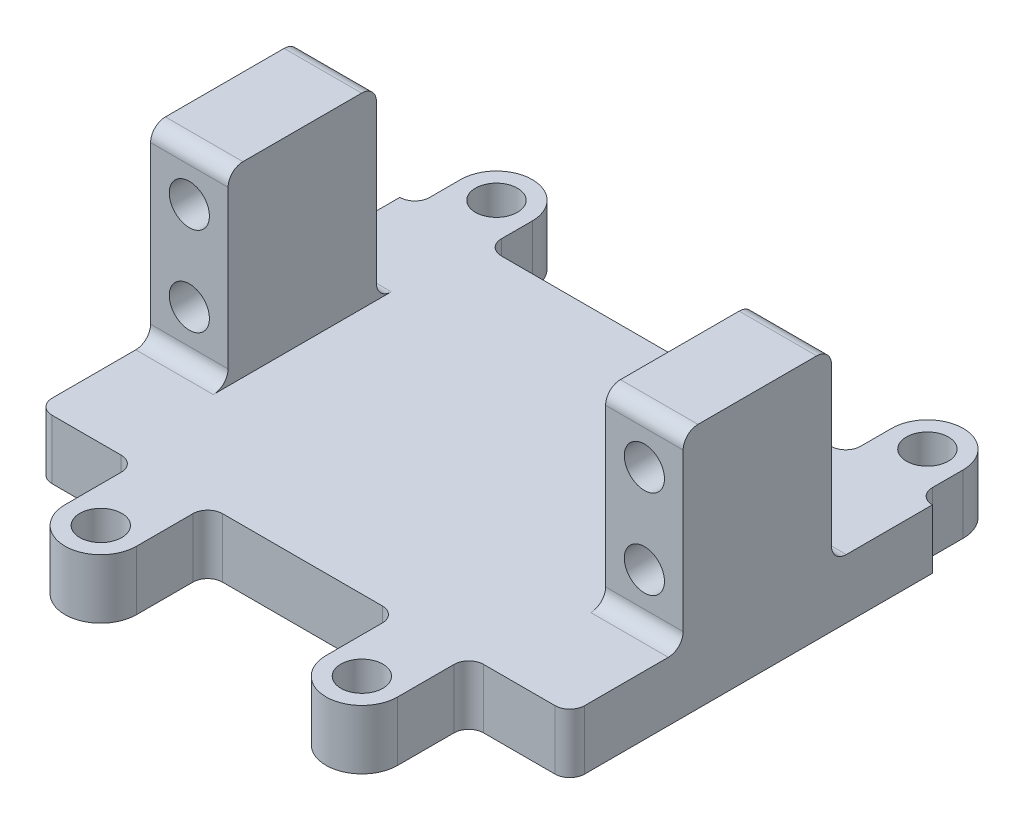
SolidWorks part; units mm, degrees
ref_plane "Front Plane" through (0, 0, 0) normal (0, 0, 1) x (1, 0, 0)
ref_plane "Top Plane" through (0, 0, 0) normal (0, 1, 0) x (1, 0, 0)
ref_plane "Right Plane" through (0, 0, 0) normal (1, 0, 0) x (0, 0, -1)
sketch "Sketch1" plane through (0, 0, 0) normal (0, 1, 0) x (1, 0, 0)
  line L1 (0, 0) -> (54.4, 0)
  line L2 (0, 0) -> (0, 38.8)
  line L3 (0, 38.8) -> (54.4, 38.8)
  line L4 (54.4, 0) -> (54.4, 38.8)
  dimension "D1" = 54.4
  dimension "D2" = 38.8
extrude "Boss-Extrude1" add sketch "Sketch1" along normal blind 3.175
sketch "Sketch2" plane through (0, 3.175, 0) normal (0, 1, 0) x (1, 0, 0)
  line L0 (0, 38.8) -> (0, 0) construction
  line L1 (0, 28) -> (7, 28)
  line L2 (0, 28) -> (0, 12.125)
  line L3 (0, 12.125) -> (7, 12.125)
  line L4 (7, 28) -> (7, 12.125)
  line L5 (54.4, 38.8) -> (0, 38.8) construction
  dimension "D1" = 15.875
  dimension "D2" = 10.8
  dimension "D3" = 7
extrude "Boss-Extrude2" add sketch "Sketch2" along normal blind 20
ref_plane "Plane1" through (27.2, 0, 0) normal (-1, 0, 0) x (0, 0, 1)
mirror "Mirror1" about plane through (27.2, 0, 0) normal (-1, 0, 0) of "Boss-Extrude2"
sketch "Sketch3" plane through (0, 3.175, 0) normal (0, 1, 0) x (1, 0, 0)
  line L0 (9.2746, -7.608) -> (9.2746, 0)
  line L1 (0, 0) -> (54.4, 0) construction
  line L2 (16.9454, -7.608) -> (16.9454, 0)
  circle A0 centre (13.11, -7.608) radius 2.2479
  circle A2 centre (13.11, -7.608) radius 3.8354
  line M12 (0, 0) -> (54.4, 0)
  dimension "D1" = 4.4958
  dimension "D4" = 1.5875
  dimension "D2" = 7.608
  dimension "D3" = 13.11
extrude "Boss-Extrude3" add sketch "Sketch3" against normal up to surface (3.175 mm away) contours A2 A0 | A2 L2 L0 M12 region at (13.11, 3.175, 2.3776) region at (13.11, 3.175, 3.8811) up to face at (27.2, 0, -19.4)
pattern_linear "LPattern1" count 2 spacing 27.94 along (1, 0, 0) of "Boss-Extrude3"
sketch "Sketch6" plane through (0, 3.175, 0) normal (0, 1, 0) x (1, 0, 0)
  line L0 (0, 38.8) -> (0, 28) construction
  line L1 (0.3048, 43.7) -> (0.3048, 38.8)
  line L2 (7.9756, 43.7) -> (7.9756, 38.8)
  line L3 (54.4, 38.8) -> (0, 38.8) construction
  circle A0 centre (4.1402, 43.7) radius 2.2479
  circle A1 centre (13.11, -7.608) radius 2.2479 construction
  circle A2 centre (4.1402, 43.7) radius 3.8354
  line M24 (54.4, 38.8) -> (0, 38.8)
  dimension "D2" = 4.4958
  dimension "D4" = 1.5875
  dimension "D1" = 51.308
  dimension "D3" = 4.1402
extrude "Boss-Extrude6" add sketch "Sketch6" against normal up to surface (3.175 mm away) contours A2 A0 | A2 L1 L2 M24 region at (4.1402, 3.175, -39.7736) region at (4.1402, 3.175, -47.4269) up to face at (27.12, 0, -3.2914)
mirror "Mirror3" about plane through (27.2, 0, 0) normal (-1, 0, 0) of "Boss-Extrude6"
sketch "Sketch7" plane through (0, 0, -28) normal (0, 0, -1) x (-1, 0, 0)
  line L0 (-7, 23.175) -> (-7, 3.175) construction
  line L1 (-7, 23.175) -> (0, 23.175) construction
  circle A0 centre (-2.8526, 17.925) radius 2.15
  circle A1 centre (-2.8526, 8.425) radius 2.15
  dimension "D1" = 4.3
  dimension "D2" = 4.1474
  dimension "D3" = 5.25
  dimension "D4" = 9.5
extrude "Cut-Extrude1" cut sketch "Sketch7" against normal up to surface (15.875 mm away) up to face at (3.5, 13.175, -12.125)
sketch "Sketch9" plane through (0, 0, 0) normal (-1, 0, 0) x (0, 0, 1)
  line L0 (-38.8, 0) -> (-38.8, 3.175) construction
  line L1 (-38.8, 0) -> (-38.8, 3.175)
  line L2 (-38.8, 3.175) -> (-28, 3.175)
  line L3 (-28, 3.175) -> (-28, 23.175)
  line L4 (-28, 23.175) -> (-12.125, 23.175)
  line L5 (-12.125, 23.175) -> (-12.125, 3.175)
  line L10 (0, 0) -> (-38.8, 0)
  line L11 (-12.125, 3.175) -> (0, 3.175)
  line L12 (0, 3.175) -> (0, 0)
extrude "Boss-Extrude7" add sketch "Sketch9" along normal blind 1.2948
mirror "Mirror4" about plane through (27.2, 0, 0) normal (-1, 0, 0) of "Boss-Extrude7"
mirror "Mirror5" about plane through (27.2, 0, 0) normal (-1, 0, 0) of "Cut-Extrude1"
sketch "Sketch11" plane through (0, 0, 0) normal (0, -1, 0) x (1, 0, 0)
  line L16 (55.6948, 0) -> (44.8854, 0)
  line L17 (-1.2948, 0) -> (-1.2948, -38.8)
  line L18 (-1.2948, -38.8) -> (0.3048, -38.8)
  line L19 (0.3048, -38.8) -> (0.3048, -43.7)
  line L20 (7.9756, -43.7) -> (7.9756, -38.8)
  line L21 (0.3048, -38.8) -> (0.3048, -43.7)
  line L22 (46.4244, -38.8) -> (46.4244, -43.7)
  line L23 (7.9756, -38.8) -> (46.4244, -38.8)
  line L24 (54.0952, -38.8) -> (55.6948, -38.8)
  line L25 (55.6948, -38.8) -> (55.6948, 0)
  line L26 (55.6948, 0) -> (44.8854, 0)
  line L27 (44.8854, 0) -> (44.8854, 7.608)
  line L28 (37.2146, 7.608) -> (37.2146, 0)
  line L29 (37.2146, 0) -> (16.9454, 0)
  line L30 (16.9454, 0) -> (16.9454, 7.608)
  line L31 (9.2746, 7.608) -> (9.2746, 0)
  line L33 (-1.2948, 0) -> (-1.2948, -38.8)
  line L34 (-1.2948, -38.8) -> (0.3048, -38.8)
  line L36 (7.9756, -43.7) -> (7.9756, -38.8)
  line L38 (46.4244, -38.8) -> (46.4244, -43.7)
  line L40 (54.0952, -38.8) -> (55.6948, -38.8)
  line L41 (55.6948, -38.8) -> (55.6948, 0)
  line L43 (44.8854, 0) -> (44.8854, 7.608)
  line L44 (37.2146, 7.608) -> (37.2146, 0)
  line L46 (16.9454, 0) -> (16.9454, 7.608)
  line L47 (9.2746, 7.608) -> (9.2746, 0)
  line L48 (37.2146, 0) -> (16.9454, 0)
  line L49 (9.2746, 0) -> (-1.2948, 0)
  line L50 (9.2746, 0) -> (-1.2948, 0)
  line L51 (7.9756, -38.8) -> (46.4244, -38.8)
  line L52 (54.0952, -43.7) -> (54.0952, -38.8)
  line L53 (54.0952, -43.7) -> (54.0952, -38.8)
  circle A0 centre (4.1402, -43.7) radius 2.2479 construction
  circle A1 centre (50.2598, -43.7) radius 2.2479 construction
  circle A2 centre (41.05, 7.608) radius 2.2479 construction
  circle A3 centre (13.11, 7.608) radius 2.2479 construction
  circle A4 centre (4.1402, -43.7) radius 2.2479
  circle A5 centre (50.2598, -43.7) radius 2.2479
  circle A6 centre (41.05, 7.608) radius 2.2479
  circle A7 centre (13.11, 7.608) radius 2.2479
  arc A16 (0.3048, -43.7) -> (7.9756, -43.7) centre (4.1402, -43.7) ccw
  arc A19 (46.4244, -43.7) -> (54.0952, -43.7) centre (50.2598, -43.7) ccw
  arc A23 (44.8854, 7.608) -> (37.2146, 7.608) centre (41.05, 7.608) ccw
  arc A26 (16.9454, 7.608) -> (9.2746, 7.608) centre (13.11, 7.608) ccw
  arc A30 (0.3048, -43.7) -> (7.9756, -43.7) centre (4.1402, -43.7) ccw
  arc A33 (46.4244, -43.7) -> (54.0952, -43.7) centre (50.2598, -43.7) ccw
  arc A37 (44.8854, 7.608) -> (37.2146, 7.608) centre (41.05, 7.608) ccw
  arc A40 (16.9454, 7.608) -> (9.2746, 7.608) centre (13.11, 7.608) ccw
  dimension "D1" = 0
extrude "Boss-Extrude8" add sketch "Sketch11" along normal blind 3.175
fillet "Fillet1" radius 1.5875 18 edges at (-1.2948, 0, 0) (0.3048, 0, -38.8) (7.9756, 0, -38.8) (46.4244, 0, -38.8) (54.0952, 0, -38.8) (55.6948, 0, 0) (44.8854, 0, 0) (37.2146, 0, 0) (16.9454, 0, 0) (9.2746, 0, 0) (2.8526, 23.175, -12.125) (2.8526, 3.175, -12.125) (2.8526, 3.175, -28) (2.8526, 23.175, -28) (51.5474, 3.175, -12.125) (51.5474, 23.175, -12.125) (51.5474, 23.175, -28) (51.5474, 3.175, -28)
